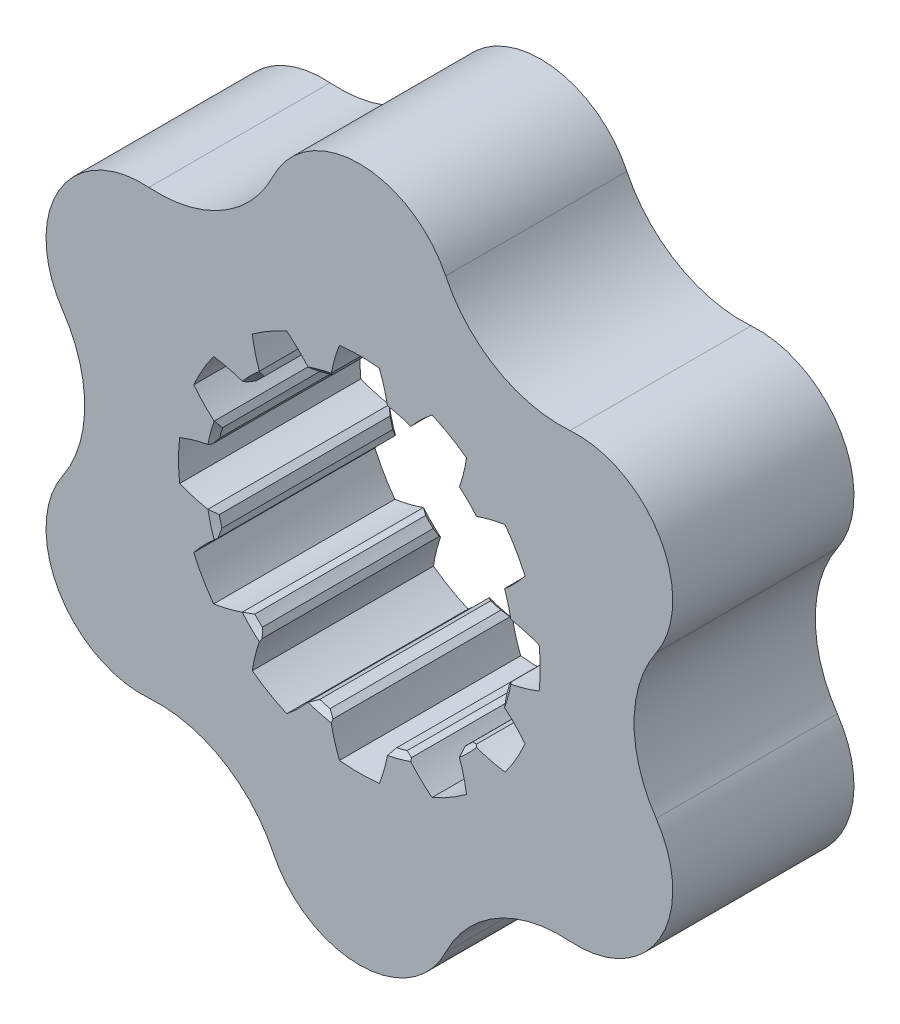
SolidWorks part; units mm, degrees
material "EN26"
ref_plane "Front Plane" through (0, 0, 0) normal (0, 0, 1) x (1, 0, 0)
ref_plane "Top Plane" through (0, 0, 0) normal (0, 1, 0) x (1, 0, 0)
ref_plane "Right Plane" through (0, 0, 0) normal (1, 0, 0) x (0, 0, -1)
sketch "Sketch1" plane through (0, 0, 0) normal (0, 0, 1) x (1, 0, 0)
  line L0 (0, 0) -> (0, 30.3913) construction
  line L1 (0, 0) -> (36.2247, 0) construction
  line L2 (0, 0) -> (26.6587, 15.3914) construction
  line L3 (0, 0) -> (15.5337, 26.9052) construction
  line L6 (0, 0) -> (-15.2602, 26.4314) construction
  circle A0 centre (0, 0) radius 26.81 construction
  circle A1 centre (0, 0) radius 21.22 construction
  circle A2 centre (0, 0) radius 11.5
  arc A3 (6.6647, 22.6258) -> (-6.6647, 22.6258) centre (0, 19.41) ccw
  arc A4 (22.9269, 5.5411) -> (16.2622, 17.0847) centre (16.8096, 9.705) ccw
  arc A5 (22.9269, -5.5411) -> (16.2622, -17.0847) centre (16.8096, -9.705) cw
  arc A6 (6.6647, -22.6258) -> (-6.6647, -22.6258) centre (0, -19.41) cw
  arc A7 (-22.9269, 5.5411) -> (-16.2622, 17.0847) centre (-16.8096, 9.705) cw
  arc A8 (-22.9269, -5.5411) -> (-16.2622, -17.0847) centre (-16.8096, -9.705) ccw
  arc A9 (6.6647, 22.6258) -> (16.2622, 17.0847) centre (15.5337, 26.9052) ccw
  arc A10 (-16.2622, 17.0847) -> (-6.6647, 22.6258) centre (-15.5337, 26.9052) ccw
  arc A11 (22.9269, 5.5411) -> (22.9269, -5.5411) centre (31.0675, 0) ccw
  arc A12 (-22.9269, 5.5411) -> (-22.9269, -5.5411) centre (-31.0675, 0) cw
  arc A13 (-6.6647, -22.6258) -> (-16.2622, -17.0847) centre (-15.5337, -26.9052) ccw
  arc A14 (6.6647, -22.6258) -> (16.2622, -17.0847) centre (15.5337, -26.9052) cw
  dimension "D1" = 42.44
  dimension "D2" = 53.62
  dimension "D3" = 23
  dimension "D6" = 14.8
  dimension "D7" = 30
  dimension "D8" = 9.8475
  dimension "D4" = 60
  dimension "D5" = 30
extrude "Extrude1" add sketch "Sketch1" along normal blind 14
chamfer "Chamfer2" distance 0.4 angle 45 2 edges at (11.5, 0, 0) (11.5, 0, 14)
sketch "Sketch2" plane through (0, 0, 0) normal (0, 0, -1) x (-1, 0, 0)
  line L0 (0, 0) -> (33.1866, 0) construction
  line L1 (0, 0) -> (0, 28.3412) construction
  arc A0 (1.54, 13.8899) -> (-1.54, 13.8899) centre (0, 0) ccw
  arc A1 (-1.54, 13.8899) -> (-2.24, 11.2797) centre (9.6643, 9.4861) ccw
  circle A2 centre (0, 0) radius 11.5 construction
  arc A3 (1.54, 13.8899) -> (2.24, 11.2797) centre (-9.6643, 9.4861) cw
  arc A4 (2.24, 11.2797) -> (-2.24, 11.2797) centre (0, 0) ccw
  dimension "D1" = 27.95
  dimension "D4" = 12.0386
  dimension "D2" = 3.08
  dimension "D3" = 4.48
extrude "Extrude2" cut sketch "Sketch2" against normal up to next
pattern_circular "CirPattern1" count 12 over 360 about axis through (0, 0, 14) along (0, 0, -1) of "Extrude2"
chamfer "Chamfer1" distance 0.25 angle 45 24 edges at (-10.8885, -3.7, 7) (-11.2797, -2.24, 7) (-3.7, -10.8885, 7) (-8.6485, -7.5798, 7) (-7.5798, -8.6485, 7) (-2.24, -11.2797, 7) (2.24, -11.2797, 7) (3.7, -10.8885, 7) (7.5798, -8.6485, 7) (8.6485, -7.5798, 7) (10.8885, -3.7, 7) (11.2797, -2.24, 7) (11.2797, 2.24, 7) (10.8885, 3.7, 7) (8.6485, 7.5798, 7) (7.5798, 8.6485, 7) (3.7, 10.8885, 7) (2.24, 11.2797, 7) (-3.7, 10.8885, 7) (-2.24, 11.2797, 7) (-7.5798, 8.6485, 7) (-8.6485, 7.5798, 7) (-10.8885, 3.7, 7) (-11.2797, 2.24, 7) first distance on face at (-11.648, -4.4152, 7.0667) first distance on face at (-11.0961, -2.9732, 7) first distance on face at (-2.9732, -11.0961, 7) first distance on face at (-8.1229, -8.1229, 7) first distance on face at (-7.8798, -9.6477, 7.0667) first distance on face at (-2.0003, -12.2951, 7.0667) first distance on face at (2.9732, -11.0961, 7) first distance on face at (4.4152, -11.648, 7.0667) first distance on face at (8.1229, -8.1229, 7) first distance on face at (9.6477, -7.8798, 7.0667) first distance on face at (11.0961, -2.9732, 7) first distance on face at (12.2951, -2.0003, 7.0667) first distance on face at (11.0961, 2.9732, 7) first distance on face at (11.648, 4.4152, 7.0667) first distance on face at (8.1229, 8.1229, 7) first distance on face at (7.8798, 9.6477, 7.0667) first distance on face at (2.9732, 11.0961, 7) first distance on face at (2.0003, 12.2951, 7.0667) first distance on face at (-4.4152, 11.648, 7.0667) first distance on face at (-2.9732, 11.0961, 7) first distance on face at (-8.1229, 8.1229, 7) first distance on face at (-9.6477, 7.8798, 7.0667) first distance on face at (-11.0961, 2.9732, 7) first distance on face at (-12.2951, 2.0003, 7.0667)
